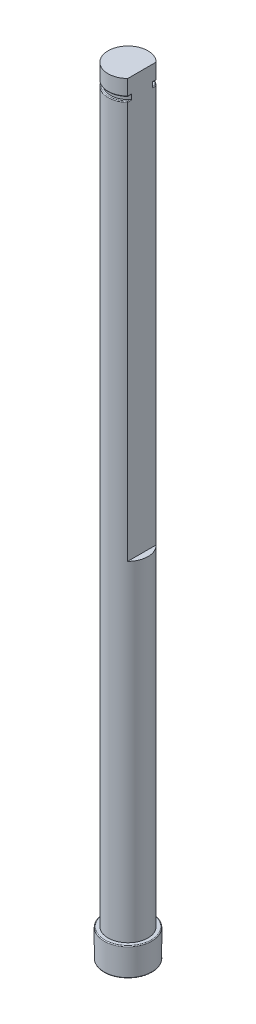
SolidWorks part; units mm, degrees
ref_plane "Front Plane" through (0, 0, 0) normal (0, 0, 1) x (1, 0, 0)
ref_plane "Top Plane" through (0, 0, 0) normal (0, 1, 0) x (1, 0, 0)
ref_plane "Right Plane" through (0, 0, 0) normal (1, 0, 0) x (0, 0, -1)
sketch "Sketch1" plane through (0, 0, 0) normal (0, 1, 0) x (1, 0, 0)
  circle A3 centre (0, 0) radius 5
  point P2 (0, 0)
  point P3 (0, 0)
  line B0 (1.8427, 2.3674) -> (1.8427, -2.3674)
  line B1 (1.8427, 2.3674) -> (1.8427, -2.3674)
  arc B2 (1.8427, -2.3674) -> (1.8427, 2.3674) centre (0, 0) ccw
  arc B3 (1.8427, 2.3674) -> (0, 3) centre (0, 0) ccw
  arc B4 (0, 3) -> (1.8427, -2.3674) centre (0, 0) ccw
  dimension "D1" = 10
sketch_block_instance "Block1-1"
sketch_block "Block1"
extrude "Boss-Extrude1" add sketch "Sketch1" along normal blind 195 contours A3 B4 B3 B2 | B3 B4 B0 | A3 region at (-4.8586, 0, 0) region at (-0.3617, 0, 0)
extrude "Cut-Extrude1" cut sketch "Sketch1<3>" along normal blind 12 contours B3 B4 B0 region at (-0.3617, 0, 0)
sketch "Sketch1<3>" plane through (0, 0, 0) normal (0, 1, 0) x (1, 0, 0) same geometry as "Sketch1"
sketch "Sketch3" plane through (0, 195, 0) normal (0, 1, 0) x (1, 0, 0)
  line L0 (3.5, 3.5707) -> (3.5, -3.5707)
  circle A0 centre (0, 0) radius 5 construction
  circle A1 centre (0, 0) radius 5
  point P5 (0, 0)
  circle M3 centre (0, 0) radius 5
  dimension "D1" = 3.5
extrude "Cut-Extrude2" cut sketch "Sketch3" against normal blind 105 contours L0 M3 region at (4.1085, 195, 0)
sketch "Sketch4" plane through (0, 195, 0) normal (0, 1, 0) x (1, 0, 0)
  line L0 (3.5, 3.5707) -> (3.5, -3.5707) construction
  line L1 (3.5, 3.5707) -> (3.5, 2.6665)
  line L2 (3.5, -2.6665) -> (3.5, -3.5707)
  arc A0 (3.5, 3.5707) -> (3.5, -3.5707) centre (0, 0) ccw construction
  arc A1 (3.5, 3.5707) -> (3.5, -3.5707) centre (0, 0) ccw
  arc A2 (10.5, 10.7121) -> (10.5, -10.7121) centre (0, 0) ccw
  arc A3 (3.5, 2.6665) -> (3.5, -2.6665) centre (0, 0) ccw
  line M5 (3.5, -3.5707) -> (3.5, 3.5707)
  arc M6 (3.5, 3.5707) -> (3.5, -3.5707) centre (0, 0) ccw
  dimension "D2" = 0.6
  dimension "D1" = 10
extrude "Cut-Extrude3" cut sketch "Sketch4" along normal blind 1 from offset 5 contours A3 M5 M6 region at (3.3688, 195, -3.1186) offset against normal yes
fillet "Fillet1" radius 0.2 6 edges at (3.5, 191, 3.1186) (3.5, 190, 3.1186) (3.5, 191, -3.1186) (3.5, 190, -3.1186) (-5, 191, 0) (-5, 190, 0)
sketch "Sketch5" plane through (0, 0, 0) normal (0, -1, 0) x (1, 0, 0)
  circle A0 centre (0, 0) radius 6
  circle A1 centre (0, 0) radius 5 construction
  circle A2 centre (0, 0) radius 5
  dimension "D1" = 1
extrude "Boss-Extrude2" add sketch "Sketch5" against normal blind 7.05
fillet "Fillet2" radius 0.2 2 edges at (0, 7.05, -6) (0, 0, -6)
